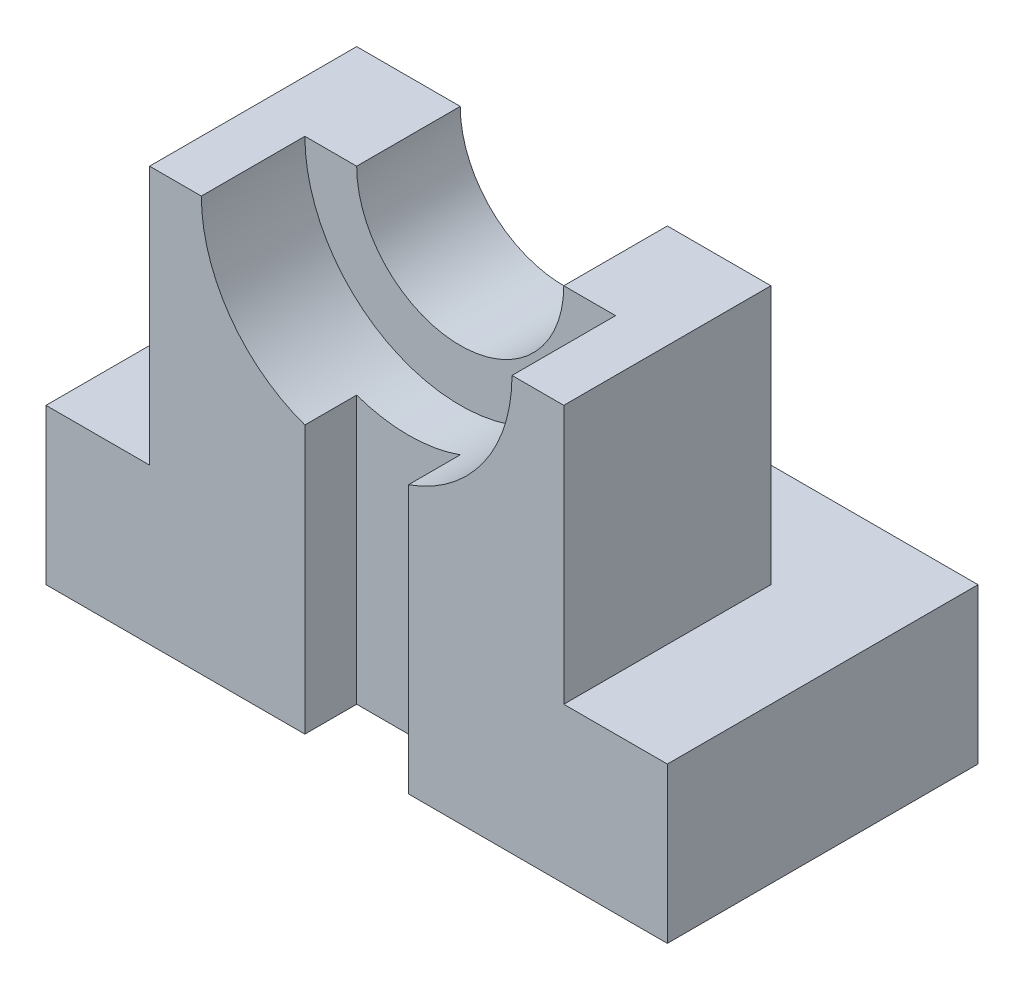
SolidWorks part; units mm, degrees
ref_plane "Front Plane" through (0, 0, 0) normal (0, 0, 1) x (1, 0, 0)
ref_plane "Top Plane" through (0, 0, 0) normal (0, 1, 0) x (1, 0, 0)
ref_plane "Right Plane" through (0, 0, 0) normal (1, 0, 0) x (0, 0, -1)
sketch "Sketch1" plane through (0, 0, 0) normal (0, 0, 1) x (1, 0, 0)
  line L0 (0, -37.5688) -> (0, 37.5688) construction
  line L1 (-20, 0) -> (20, 0)
  line L2 (-20, 0) -> (-20, -25)
  line L3 (-20, -25) -> (20, -25)
  line L4 (20, 0) -> (20, -25)
  line L5 (-20, -25) -> (-30, -25)
  line L6 (-30, -25) -> (-30, -40)
  line L7 (-30, -40) -> (30, -40)
  line L8 (30, -40) -> (30, -25)
  line L9 (30, -25) -> (20, -25)
  point P9 (0, 0)
  dimension "D1" = 40
  dimension "D2" = 60
  dimension "D3" = 25
  dimension "D4" = 15
extrude "Boss-Extrude1" add sketch "Sketch1" along normal blind 20 contours L0 L3 L4 L1 | L3 L0 L1 L2 region at (-10, -12.5, 0) region at (10, -12.5, 0)
extrude "Boss-Extrude2" add sketch "Sketch1<3>" against normal blind 10 and the other way blind 20 contours L8 L9 L3 L5 L6 L7 region at (0, -32.5, 0)
sketch "Sketch1<3>" plane through (0, 0, 0) normal (0, 0, 1) x (1, 0, 0) same geometry as "Sketch1"
sketch "Sketch2" plane through (0, 0, 20) normal (0, 0, 1) x (1, 0, 0)
  circle A0 centre (0, 0) radius 10
  dimension "D1" = 10
extrude "Cut-Extrude1" cut sketch "Sketch2" against normal through all
sketch "Sketch3" plane through (0, 0, 0) normal (0, 1, 0) x (1, 0, 0)
  line L0 (0, -25.2651) -> (0, 25.2651) construction
  line L2 (-5, -20) -> (-5, -15)
  line L3 (-10, -20) -> (10, -20) construction
  line L4 (-5, -15) -> (5, -15)
  line L5 (5, -15) -> (5, -20)
  line L6 (5, -20) -> (-5, -20)
  point P4 (0, 0)
  dimension "D1" = 10
  dimension "D2" = 5
extrude "Cut-Extrude2" cut sketch "Sketch3" against normal through all
sketch "Sketch4" plane through (0, 0, 20) normal (0, 0, 1) x (1, 0, 0)
  circle A0 centre (0, 0) radius 15
  dimension "D1" = 15
extrude "Cut-Extrude3" cut sketch "Sketch4" against normal blind 10
